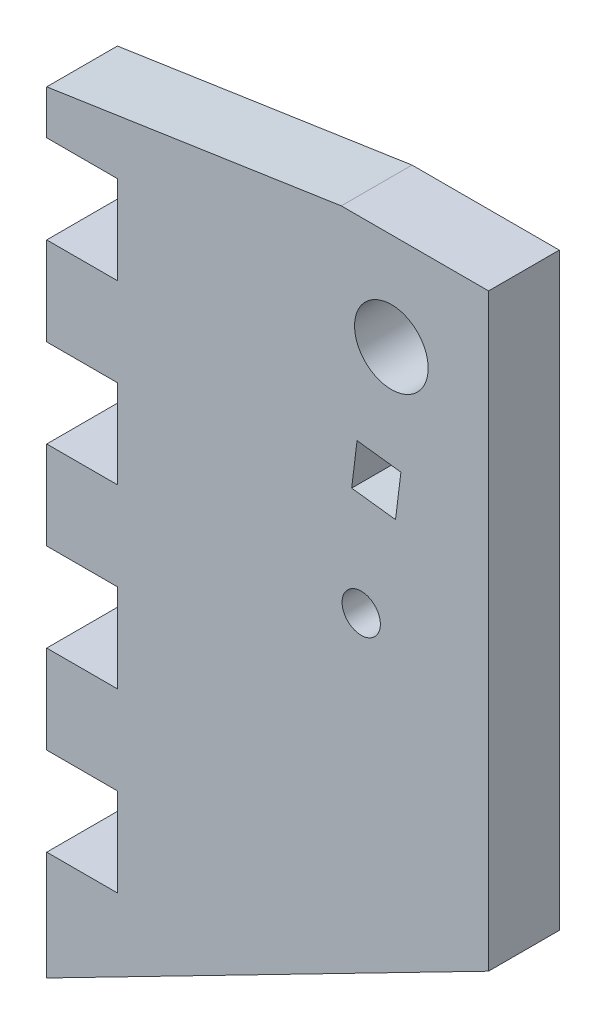
SolidWorks part; units mm, degrees
material "Thornel VCB-20 Carbon Cloth"
ref_plane "Front Plane" through (0, 0, 0) normal (0, 0, 1) x (1, 0, 0)
ref_plane "Top Plane" through (0, 0, 0) normal (0, 1, 0) x (1, 0, 0)
ref_plane "Right Plane" through (0, 0, 0) normal (1, 0, 0) x (0, 0, -1)
sketch "Sketch1" plane through (0, 0, 0) normal (0, 0, 1) x (1, 0, 0)
  line L0 (0, 0) -> (-38.1, 0)
  line L1 (0, 0) -> (0, -50.8)
  line L2 (-38.1, 0) -> (-38.1, -7.62)
  line L3 (-38.1, -7.62) -> (-32.004, -7.62)
  line L4 (-32.004, -7.62) -> (-32.004, -15.24)
  line L5 (-32.004, -15.24) -> (-38.1, -15.24)
  line L6 (-38.1, -45.72) -> (-38.1, -70.358)
  line L7 (-38.1, -15.24) -> (-38.1, -22.86)
  line L8 (-38.1, -22.86) -> (-32.004, -22.86)
  line L9 (-32.004, -22.86) -> (-32.004, -30.48)
  line L10 (-32.004, -30.48) -> (-38.1, -30.48)
  line L11 (-38.1, -30.48) -> (-38.1, -38.1)
  line L12 (-38.1, -38.1) -> (-32.004, -38.1)
  line L13 (-32.004, -38.1) -> (-32.004, -45.72)
  line L14 (-32.004, -45.72) -> (-38.1, -45.72)
  line L15 (-38.1, -70.358) -> (0, -50.8)
  circle A0 centre (-8.382, -8.382) radius 3.175
  dimension "D9" = 6.35
  dimension "D1" = 38.1
  dimension "D2" = 50.8
  dimension "D3" = 7.62
  dimension "D4" = 7.62
  dimension "D6" = 6.096
  dimension "D8" = 70.358
  dimension "D12" = 8.382
  dimension "D13" = 8.382
  dimension "D7" = 3
extrude "Boss-Extrude1" add sketch "Sketch1" along normal blind 6.096 contours L6 L15 L1 L0 L2 L3 L4 L5 L7 L8 L9 L10 L11 L12 L13 L14 A0 region at (-19.2717, -31.1343, 0)
sketch "Sketch2" plane through (0, 0, 0) normal (0, 0, -1) x (-1, 0, 0)
  line L5 (38.1, 0) -> (12.7, 0)
  line L6 (0, 0) -> (38.1, 0) construction
  line L7 (12.7, 0) -> (38.1, -3.81)
  line L8 (38.1, 0) -> (38.1, -7.62) construction
  line L9 (38.1, -3.81) -> (38.1, 0)
  dimension "D1" = 25.4
  dimension "D2" = 3.81
extrude "Cut-Extrude1" cut sketch "Sketch2" against normal blind 8.636
sketch "Sketch4" plane through (0, 0, 6.096) normal (0, 0, 1) x (1, 0, 0)
  line L0 (-38.1, -45.72) -> (-38.1, -53.34)
  line L1 (-38.1, -45.72) -> (-38.1, -70.358) construction
  line L2 (-38.1, -53.34) -> (-32.004, -53.34)
  line L3 (-32.004, -53.34) -> (-32.004, -60.96)
  line L4 (-32.004, -60.96) -> (-38.1, -60.96)
  line L5 (-38.1, -60.96) -> (-38.1, -53.34)
  line M18 (-38.1, -45.72) -> (-38.1, -70.358)
  dimension "D1" = 7.62
  dimension "D2" = 6.096
  dimension "D3" = 6.096
  dimension "D4" = 7.62
extrude "Cut-Extrude2" cut sketch "Sketch4" against normal through all contours L4 L3 L2 M18 region at (-35.052, -57.15, 6.096)
sketch "Sketch5" plane through (0, 0, 0) normal (0, 0, -1) x (-1, 0, 0)
  line L0 (8.382, -8.382) -> (10.9822, -29.559) construction
  line L1 (8.382, -8.382) -> (8.382, -39.2411) construction
  line L2 (7.5591, -17.3118) -> (11.3407, -16.8475)
  line L3 (7.5591, -17.3118) -> (8.0235, -21.0934)
  line L4 (8.0235, -21.0934) -> (11.8051, -20.6291)
  line L5 (11.3407, -16.8475) -> (11.8051, -20.6291)
  circle A0 centre (8.382, -8.382) radius 3.175 construction
  circle A1 centre (10.9822, -29.559) radius 1.651
  dimension "D3" = 8.763
  dimension "D1" = 21.336
  dimension "D2" = 7
  dimension "D4" = 1.905
  dimension "D5" = 3.81
  dimension "D6" = 3.81
extrude "Cut-Extrude4" cut sketch "Sketch5" against normal up to surface (6.096 mm away) up to face at (-5.207, -8.382, 6.096)
ref_plane "Plane1" through (0, 0, 0) normal (0, 0, -1) x (-1, 0, 0)
